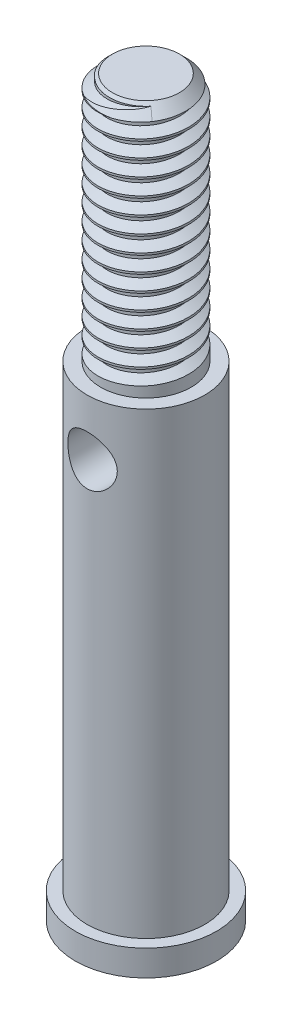
SolidWorks part; units mm, degrees
ref_plane "Front Plane" through (0, 0, 0) normal (0, 0, 1) x (1, 0, 0)
ref_plane "Top Plane" through (0, 0, 0) normal (0, 1, 0) x (1, 0, 0)
ref_plane "Right Plane" through (0, 0, 0) normal (1, 0, 0) x (0, 0, -1)
sketch "Sketch1" plane through (0, 0, 0) normal (0, 1, 0) x (1, 0, 0)
  circle A0 centre (0, 0) radius 3
  dimension "D1" = 6
extrude "Boss-Extrude1" add sketch "Sketch1" along normal blind 1.1
sketch "Sketch2" plane through (0, 1.1, 0) normal (0, 1, 0) x (1, 0, 0)
  circle A0 centre (0, 0) radius 2.5
  dimension "D1" = 5
extrude "Boss-Extrude2" add sketch "Sketch2" along normal blind 19.5
sketch "Sketch3" plane through (0, 20.6, 0) normal (0, 1, 0) x (1, 0, 0)
  circle A0 centre (0, 0) radius 1.925
  dimension "D1" = 3.85
extrude "Boss-Extrude3" add sketch "Sketch3" along normal blind 10.6
chamfer "Chamfer1" distance 0.5 angle 45 1 edges at (0, 31.2, 1.925)
thread "Thread1" pitch 0.7 start angle 0, offset 0.7, length 0, pitch 0.7, diameter 3.85
ref_plane "Plane1" through (-1.925, 31.9, 0) normal (0, 0, 1) x (-1, 0, 0)
sketch "Thread Profile1" plane through (-1.925, 31.9, 0) normal (0, 0, 1) x (-1, 0, 0)
  line L0 (0, 0) -> (0, 0.7) construction
  line L11 (0, 0) -> (0, 0.6125)
  line L12 (0, 0.6125) -> (-0.3789, 0.3937)
  line L13 (-0.3789, 0.3937) -> (-0.3789, 0.2187)
  line L15 (-0.3789, 0.2187) -> (0, 0)
  line L17 (-0.3789, 0.3062) -> (0, 0.3062) construction
  point P2 (0, 0)
  dimension "Pitch" = 0.7
  dimension "Profile_Angle" = 60
  dimension "Profile_Land" = 0.175
  dimension "Profile_Height" = 0.3789
ref_plane "Plane2" through (0, 0, 2.5) normal (0, 0, 1) x (1, 0, 0)
sketch "Sketch8" plane through (0, 0, 2.5) normal (0, 0, 1) x (1, 0, 0)
  line L0 (0, 0) -> (0, 20.6) construction
  line L1 (2.5, 20.6) -> (-2.5, 20.6) construction
  line L2 (0, 17.15) -> (2.5, 17.15) construction
  line L3 (2.5, 1.1) -> (2.5, 20.6) construction
  circle A0 centre (0, 18.2) radius 1.05
  dimension "D1" = 2.1
  dimension "D2" = 17.15
extrude "Cut-Extrude1" cut sketch "Sketch8" against normal up to next
